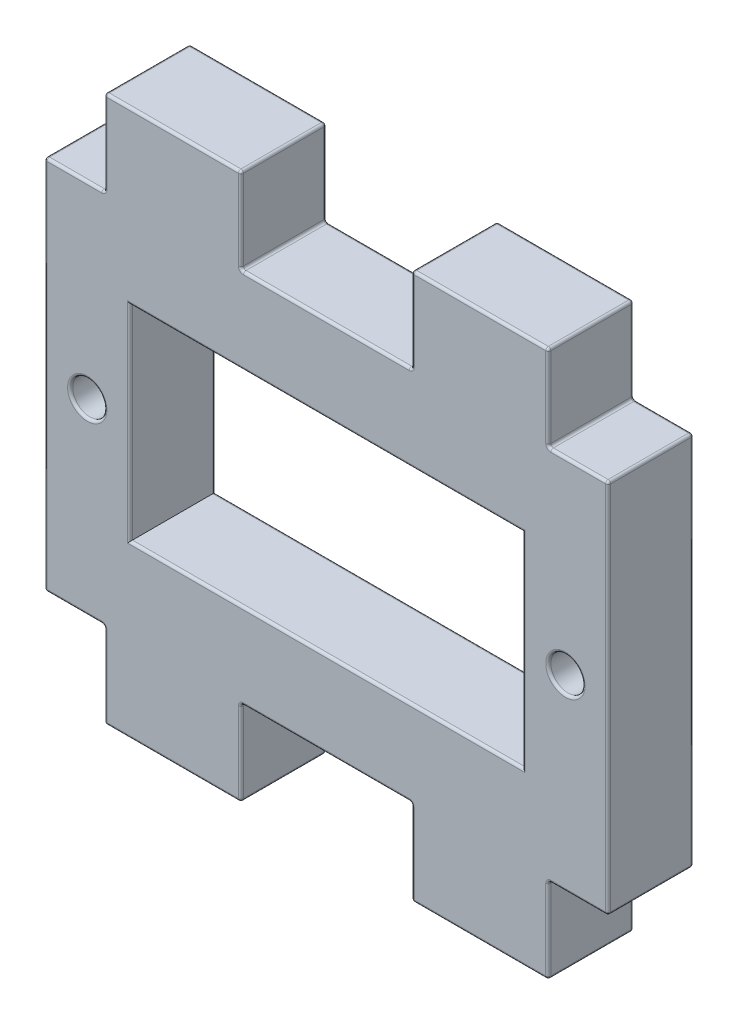
SolidWorks part; units mm, degrees
ref_plane "Płaszczyzna przednia" through (0, 0, 0) normal (0, 0, 1) x (1, 0, 0)
ref_plane "Płaszczyzna górna" through (0, 0, 0) normal (0, 1, 0) x (1, 0, 0)
ref_plane "Płaszczyzna prawa" through (0, 0, 0) normal (1, 0, 0) x (0, 0, -1)
sketch "Szkic1" plane through (0, 0, 0) normal (0, 0, 1) x (1, 0, 0)
  line L0 (-16.5, 11) -> (16.5, 11)
  line L1 (-11.5, -6) -> (11.5, -6)
  line L2 (-11.5, -6) -> (-11.5, 6)
  line L3 (-11.5, 6) -> (11.5, 6)
  line L4 (11.5, -6) -> (11.5, 6)
  line L5 (-11.5, -6) -> (11.5, 6) construction
  line L6 (-11.5, 6) -> (11.5, -6) construction
  line L7 (16.5, -11) -> (16.5, 11)
  line L8 (-16.5, -11) -> (16.5, -11)
  line L9 (-16.5, -11) -> (-16.5, 11)
  line L10 (0, 0) -> (0, 6) construction
  line L11 (-13, 11) -> (-5, 11)
  line L12 (-13, 11) -> (-13, 16)
  line L13 (-13, 16) -> (-5, 16)
  line L14 (-5, 11) -> (-5, 16)
  line L15 (0, 0) -> (-16.5, 0) construction
  line L16 (5, 11) -> (5, 16)
  line L17 (13, 16) -> (5, 16)
  line L18 (13, 11) -> (13, 16)
  line L19 (13, -11) -> (13, -16)
  line L20 (13, -16) -> (5, -16)
  line L21 (5, -11) -> (5, -16)
  line L22 (-5, -11) -> (-5, -16)
  line L23 (-13, -16) -> (-5, -16)
  line L24 (-13, -11) -> (-13, -16)
  circle A0 centre (-14, 0) radius 1
  circle A1 centre (14, 0) radius 1
  point P0 (0, 0)
  dimension "D7" = 2
  dimension "D1" = 12
  dimension "D2" = 23
  dimension "D4" = 3.5
  dimension "D5" = 5
  dimension "D6" = 8
  dimension "D8" = 2.5
  dimension "D3" = 5
extrude "Dodanie-wyciągnięcie1" add sketch "Szkic1" along normal mid plane 5 contours L9 L8 L7 L0 L4 L1 L2 L3 A0 A1 | L8 L24 L23 L22 | L8 L21 L20 L19 | L0 L18 L17 L16 | L0 L14 L13 L12 region at (-14.75, 10.6034, 0) region at (-9, 13.5, 0) region at (-9, -13.5, 0) region at (9, 13.5, 0) region at (9, -13.5, 0)
fillet "Zaokrąglenie1" radius 0.15 60 edges at (-13, 16, 0) (-9, 16, -2.5) (-13, 13.5, -2.5) (-9, 16, 2.5) (-5, 16, 0) (-13, 13.5, 2.5) (-13, 11, 0) (-5, 13.5, -2.5) (-14.75, 11, -2.5) (-5, 13.5, 2.5) (-5, 11, 0) (-14.75, 11, 2.5) (-16.5, 11, 0) (0, 11, -2.5) (-16.5, 0, -2.5) (0, 11, 2.5) (5, 11, 0) (-16.5, 0, 2.5) (-16.5, -11, 0) (5, 13.5, -2.5) (-14.75, -11, -2.5) (5, 13.5, 2.5) (5, 16, 0) (-13, -11, 0) (-14.75, -11, 2.5) (9, 16, -2.5) (-13, -13.5, -2.5) (13, 16, 0) (9, 16, 2.5) (-13, -16, 0) (-13, -13.5, 2.5) (13, 13.5, -2.5) (-9, -16, -2.5) (13, 13.5, 2.5) (13, 11, 0) (-5, -16, 0) (-9, -16, 2.5) (14.75, 11, -2.5) (-5, -13.5, -2.5) (14.75, 11, 2.5) (16.5, 11, 0) (-5, -13.5, 2.5) (-5, -11, 0) (16.5, 0, -2.5) (0, -11, -2.5) (16.5, -11, 0) (16.5, 0, 2.5) (5, -11, 0) (0, -11, 2.5) (14.75, -11, -2.5) (5, -13.5, -2.5) (14.75, -11, 2.5) (13, -11, 0) (5, -16, 0) (5, -13.5, 2.5) (13, -13.5, -2.5) (9, -16, -2.5) (13, -13.5, 2.5) (9, -16, 2.5) (13, -16, 0)
fillet "Zaokrąglenie2" radius 0.15 12 edges at (15, 0, -2.5) (-13, 0, -2.5) (0, -6, -2.5) (-11.5, 0, -2.5) (0, 6, -2.5) (11.5, 0, -2.5) (0, 6, 2.5) (-11.5, 0, 2.5) (0, -6, 2.5) (11.5, 0, 2.5) (-13, 0, 2.5) (15, 0, 2.5)
